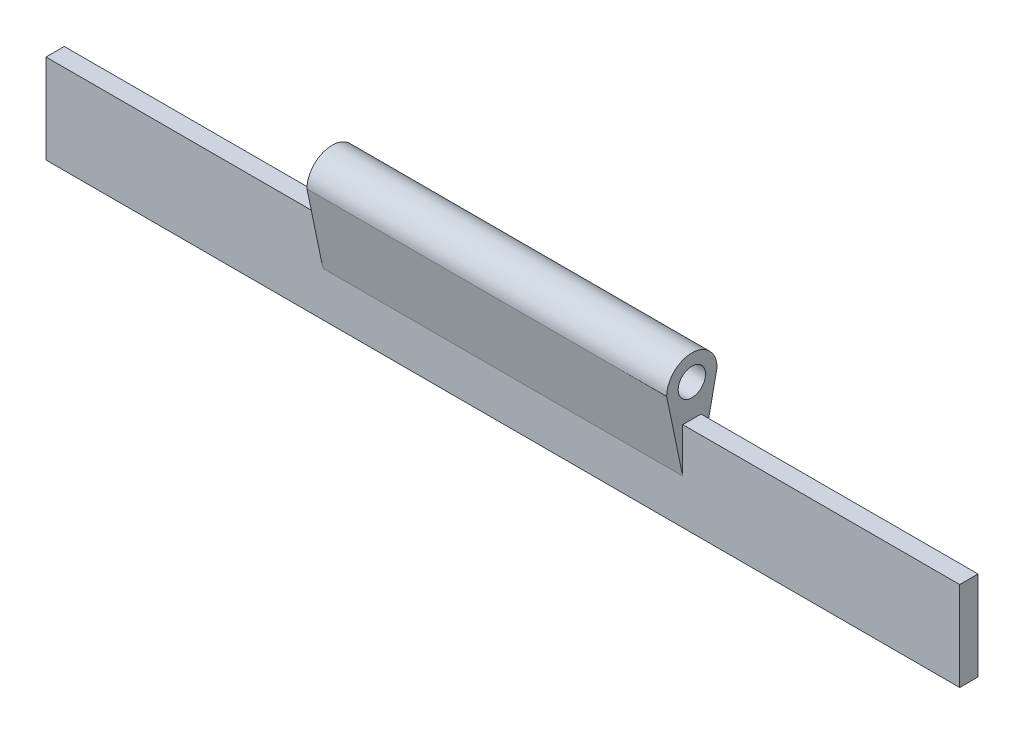
SolidWorks part; units mm, degrees
ref_plane "Front Plane" through (0, 0, 0) normal (0, 0, 1) x (1, 0, 0)
ref_plane "Top Plane" through (0, 0, 0) normal (0, 1, 0) x (1, 0, 0)
ref_plane "Right Plane" through (0, 0, 0) normal (1, 0, 0) x (0, 0, -1)
sketch "Sketch1" plane through (0, 0, 0) normal (0, 0, 1) x (1, 0, 0)
  line L0 (-63.5, 27.8) -> (-63.5, 2.4) construction
  line L1 (-63.5, 12.4) -> (63.5, 12.4)
  line L2 (-63.5, 12.4) -> (-63.5, 0)
  line L3 (-63.5, 0) -> (63.5, 0)
  line L4 (63.5, 12.4) -> (63.5, 0)
  dimension "D1" = 12.4
  dimension "D2" = 12.4
extrude "Boss-Extrude1" add sketch "Sketch1" along normal blind 2.54
sketch "Sketch2" plane through (0, 0, 0) normal (1, 0, 0) x (0, 0, -1)
  line L6 (-1.27, 12.4) -> (-1.27, 16.9) construction
  line L7 (-2.54, 12.4) -> (0, 12.4) construction
  line L8 (-2.54, 6.2) -> (-4.77, 16.9)
  line L10 (-2.54, 0) -> (-2.54, 12.4) construction
  line L11 (0, 6.2) -> (2.23, 16.9)
  line L12 (0, 0) -> (0, 12.4) construction
  line L13 (-2.54, 6.2) -> (0, 6.2)
  circle A2 centre (-1.27, 16.9) radius 1.9
  arc A3 (2.23, 16.9) -> (-4.77, 16.9) centre (-1.27, 16.9) ccw
  circle A5 centre (-1.27, 16.9) radius 3.5 construction
  point P17 (1.1303, 15.6339)
  dimension "D1" = 4.5
  dimension "D2" = 3.8
  dimension "D3" = 1.6
extrude "Boss-Extrude3" add sketch "Sketch2" along normal blind 25
extrude "Boss-Extrude4" add sketch "Sketch2<2>" against normal blind 25
sketch "Sketch2<2>" plane through (0, 0, 0) normal (1, 0, 0) x (0, 0, -1) same geometry as "Sketch2"
